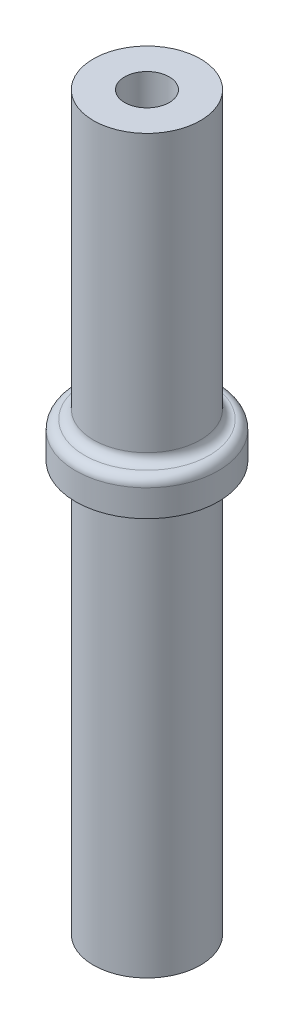
SolidWorks part; units mm, degrees
material "6061-T6 (SS)"
ref_plane "Front Plane" through (0, 0, 0) normal (0, 0, 1) x (1, 0, 0)
ref_plane "Top Plane" through (0, 0, 0) normal (0, 1, 0) x (1, 0, 0)
ref_plane "Right Plane" through (0, 0, 0) normal (1, 0, 0) x (0, 0, -1)
sketch "Sketch1" plane through (0, 0, 0) normal (0, 1, 0) x (1, 0, 0)
  circle A0 centre (0, 0) radius 3
  circle A1 centre (0, 0) radius 2 construction
  dimension "D1" = 6
  dimension "D2" = 4
extrude "Boss-Extrude1" add sketch "Sketch1" along normal blind 20.5 and the other way blind 20.5
sketch "Sketch2" plane through (0, 20.5, 0) normal (0, 1, 0) x (1, 0, 0)
  point P0 (0, 0)
hole_wizard "M3x0.5 Tapped Hole1" positions "Sketch4" profile "Sketch5" tap size "M3x0.5" standard "ANSI Metric"
sketch "Sketch4" plane through (0, 20.5, 0) normal (0, 1, 0) x (1, 0, 0)
  point P0 (0, 0)
sketch "Sketch5" plane through (0, 20.5, 0) normal (1, 0, 0) x (0, 0, 1)
  line L0 (0, 0) -> (0, 8.7511)
  line L1 (0, 8.7511) -> (1.25, 8)
  line L2 (1.25, 8) -> (1.25, 0)
  line L5 (1.25, 0) -> (0, 0)
  line L10 (0, 8.7511) -> (-1.25, 8) construction
  line L11 (0, -6.35) -> (0, 107.95) construction
  dimension "Tap Drill Dia." = 2.5
  dimension "Tap Drill Depth" = 8
  dimension "Drill Angle" = 118
cosmetic thread "Hole Thread1" parameters "D1"=6, "D2"=3
ref_plane "Plane1" through (0, 2.5, 0) normal (0, 1, 0) x (1, 0, 0)
sketch "Sketch6" plane through (0, 2.5, 0) normal (0, 1, 0) x (1, 0, 0)
  circle A0 centre (0, 0) radius 4
  dimension "D1" = 8
extrude "Boss-Extrude2" add sketch "Sketch6" along normal blind 2
mirror "Mirror1" about plane through (0, 0, 0) normal (0, 1, 0) of "M3x0.5 Tapped Hole1"
fillet "Fillet1" radius 0.5 2 edges at (0, 4.5, 4) (0, 4.5, 3)
